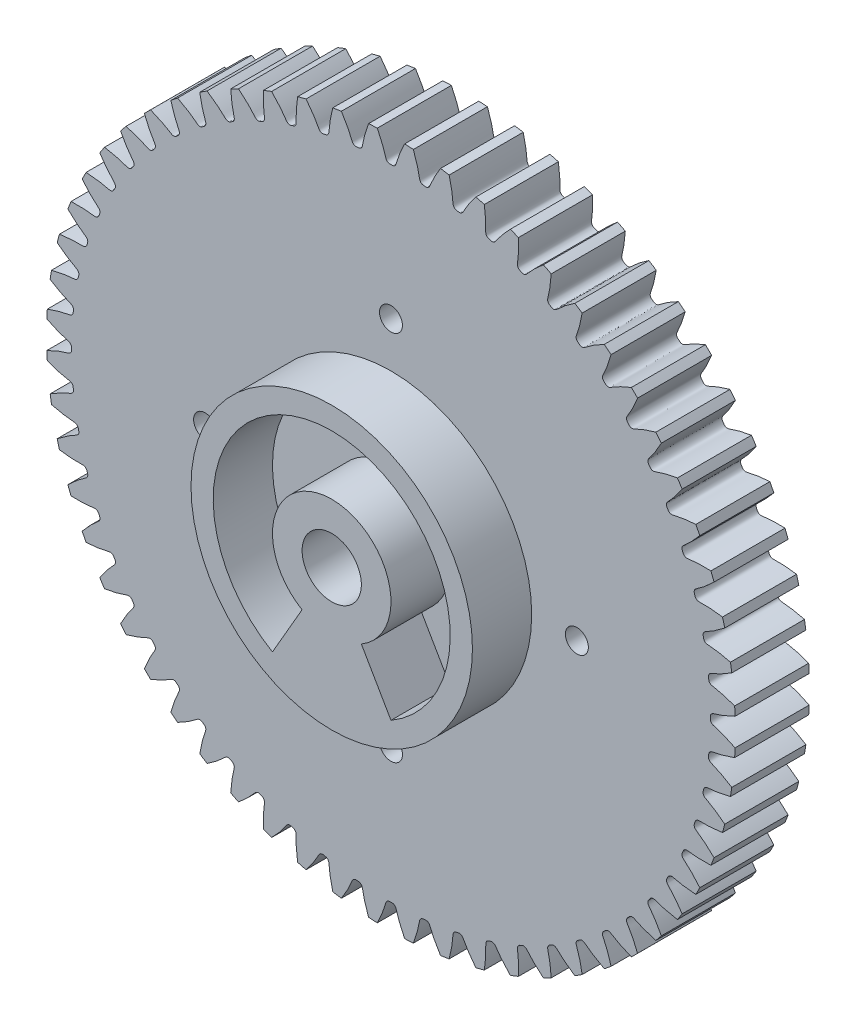
SolidWorks part; units mm, degrees
ref_plane "Front Plane" through (0, 0, 0) normal (0, 0, 1) x (1, 0, 0)
ref_plane "Top Plane" through (0, 0, 0) normal (0, 1, 0) x (1, 0, 0)
ref_plane "Right Plane" through (0, 0, 0) normal (1, 0, 0) x (0, 0, -1)
ref_axis "Axis1" through (0, 0, 5.5) along (0, 0, -1)
sketch "SketchRevolveSpurAssembly01Gear" plane through (0, 0, 0) normal (1, 0, 0) x (0, 0, -1)
  line L0 (0, 0) -> (1, 0) construction
  line L1 (-5, 0) -> (-5, 46.5)
  line L2 (-5, 46.5) -> (5, 46.5)
  line L3 (5, 46.5) -> (5, 0)
  line L4 (5, 0) -> (-5, 0)
  dimension "Side1" = 5
  dimension "OutsideRadius" = 46.5
  dimension "Side2" = 5
revolve "SpurAssembly01Gear" add sketch "SketchRevolveSpurAssembly01Gear" angle 360 about L0
sketch "SketchToothSpurAssembly01Gear" plane through (0, 0, 0) normal (0, 0, 1) x (1, 0, 0)
  arc A0 (46.5369, 1.8824) -> (46.5369, -1.8824) centre (0, 0) cw
  spline S0 degree 3 poles (46.5369, -1.8824) (46.4106, -1.8178) (46.2223, -1.724) (45.9725, -1.6049) (45.7913, -1.5209) (45.614, -1.4411) (45.4406, -1.3655) (45.2713, -1.2938) (45.1061, -1.2261) (44.945, -1.1621) (44.7882, -1.1018) (44.6356, -1.0452) (44.4874, -0.992) (44.3436, -0.9422) (44.2043, -0.8957) (44.0695, -0.8523) (43.9392, -0.8123) (43.7554, -0.7565) (43.5912, -0.7185) (43.4569, -0.6604) (43.397, -0.6284) (43.3333, -0.5856) (43.2647, -0.5249) (43.195, -0.4361) (43.14, -0.3154) (43.1191, -0.1635) (43.1282, 0) (43.1191, 0.1635) (43.14, 0.3154) (43.195, 0.4361) (43.2647, 0.5249) (43.3333, 0.5856) (43.397, 0.6284) (43.4569, 0.6604) (43.5912, 0.7185) (43.7554, 0.7565) (43.9392, 0.8123) (44.0695, 0.8523) (44.2043, 0.8957) (44.3436, 0.9422) (44.4874, 0.992) (44.6356, 1.0452) (44.7882, 1.1018) (44.945, 1.1621) (45.1061, 1.2261) (45.2713, 1.2938) (45.4406, 1.3655) (45.614, 1.4411) (45.7913, 1.5209) (45.9725, 1.6049) (46.2223, 1.724) (46.4106, 1.8178) (46.5369, 1.8824) knots 0 0 0 0 0.051766 0.076686 0.100963 0.124598 0.147592 0.169943 0.191651 0.212718 0.233143 0.252925 0.272065 0.290563 0.308419 0.325633 0.342204 0.358133 0.395729 0.403327 0.411415 0.420483 0.431261 0.444675 0.461387 0.478965 0.5 0.521035 0.538613 0.555325 0.568739 0.579517 0.588585 0.596673 0.604271 0.641867 0.657796 0.674367 0.691581 0.709437 0.727935 0.747075 0.766857 0.787282 0.808349 0.830057 0.852408 0.875402 0.899037 0.923314 0.948234 1 1 1 1
extrude "ToothExtrudeCutSpurAssembly01Gear" cut sketch "SketchToothSpurAssembly01Gear" against normal blind 5 and the other way blind 5
pattern_circular "PatternSpurAssembly01Gear" count 60 over 360 about axis through (0, 0, 5.5) along (0, 0, -1) of "ToothExtrudeCutSpurAssembly01Gear"
sketch "AuxiliarySketchSpurAssembly01Gear" plane through (0, 0, 0) normal (0, 0, 1) x (1, 0, 0)
  circle A0 centre (0, 0) radius 45 construction
  circle A1 centre (0, 0) radius 42.2862 construction
  circle A2 centre (0, 0) radius 43.6372 construction
  circle A3 centre (0, 0) radius 46.5 construction
  circle A4 centre (0, 0) radius 43.125 construction
  dimension "PitchDiameter" = 90
  dimension "BaseDiameter" = 84.5723
  dimension "FormDiameter" = 87.2745
  dimension "MajorDiameter" = 93
  dimension "MinorDiameter" = 86.25
sketch "Sketch3" plane through (0, 0, 5) normal (0, 0, 1) x (1, 0, 0)
  circle A0 centre (0, 0) radius 4
sketch "Sketch4" plane through (0, 0, 5) normal (0, 0, 1) x (1, 0, 0)
  line L0 (0, 0) -> (-9.5, -16.4545) construction
  line L1 (0, 0) -> (9.5, -16.4545) construction
  line L2 (-4, -6.9282) -> (-8, -13.8564)
  line L3 (4, -6.9282) -> (8, -13.8564)
  circle A0 centre (0, 0) radius 19
  arc A1 (8, -13.8564) -> (-8, -13.8564) centre (0, 0) ccw
  arc A2 (4, -6.9282) -> (-4, -6.9282) centre (0, 0) ccw
extrude "Boss-Extrude1" add sketch "Sketch4" along normal blind 8
sketch "Sketch5" plane through (0, 0, -5) normal (0, 0, -1) x (-1, 0, 0)
  circle A0 centre (0, 0) radius 4
extrude "Cut-Extrude2" cut sketch "Sketch5" against normal blind 18
sketch "Sketch6" plane through (0, 0, -5) normal (0, 0, -1) x (-1, 0, 0)
  circle A0 centre (25.1, 0) radius 1.55
extrude "Cut-Extrude3" cut sketch "Sketch6" against normal blind 10
pattern_circular "CirPattern2" count 4 over 360 about axis through (0, 0, 5.5) along (0, 0, -1) of "Cut-Extrude3"
